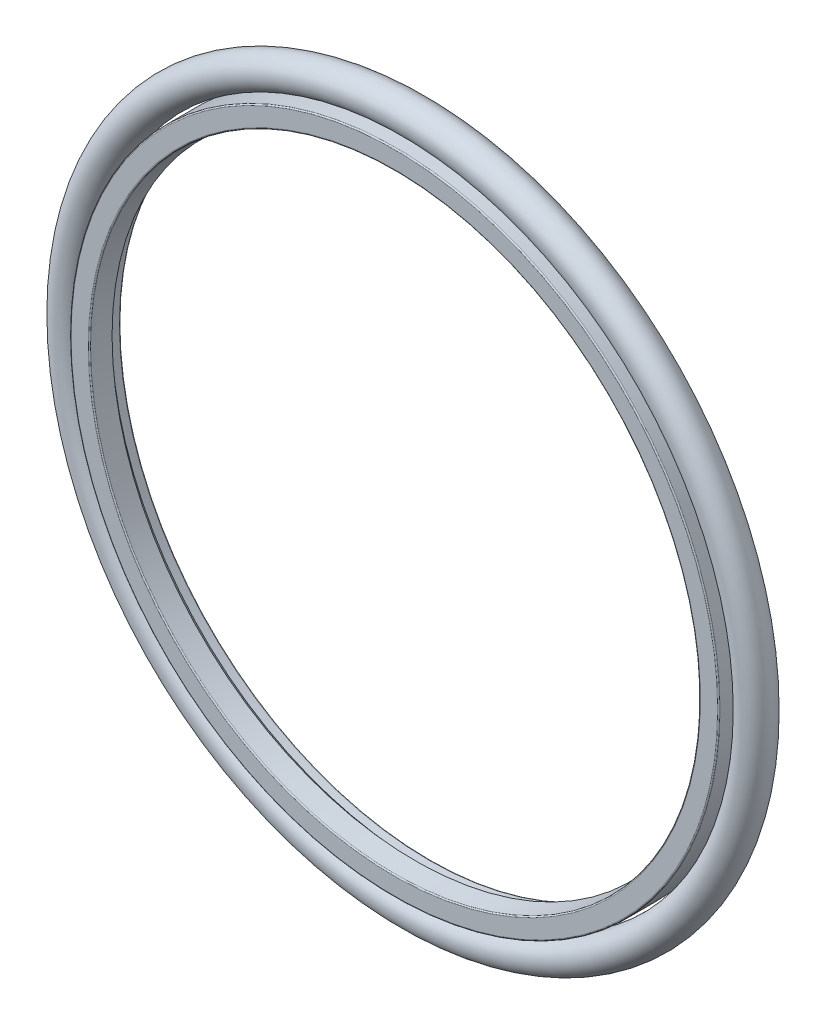
SolidWorks part; units mm, degrees
material "PTFE+NBR"
ref_plane "Front Plane" through (0, 0, 0) normal (0, 0, 1) x (1, 0, 0)
ref_plane "Top Plane" through (0, 0, 0) normal (0, 1, 0) x (1, 0, 0)
ref_plane "Right Plane" through (0, 0, 0) normal (1, 0, 0) x (0, 0, -1)
sketch "Sketch1" plane through (0, 0, 0) normal (1, 0, 0) x (0, 0, -1)
  line L0 (0, 51.05) -> (0, 53.05)
  line L1 (-0.2, 53.25) -> (-5.72, 53.25)
  line L2 (-5.92, 53.05) -> (-5.92, 50.2332)
  line L3 (-5.7375, 50.034) -> (-2.5, 49.75)
  line L5 (-1.5, 50.85) -> (-2.5, 49.75)
  line L6 (0, 0) -> (-16.4728, 0) construction
  line L7 (-0.2, 50.85) -> (-1.5, 50.85)
  arc A0 (-0.2, 53.25) -> (0, 53.05) centre (-0.2, 53.05) cw
  arc A1 (0, 51.05) -> (-0.2, 50.85) centre (-0.2, 51.05) cw
  arc A3 (-5.92, 50.2332) -> (-5.7375, 50.034) centre (-5.72, 50.2332) ccw
  arc A4 (-5.72, 53.25) -> (-5.92, 53.05) centre (-5.72, 53.05) ccw
  point P11 (0, 50.85)
  point P19 (-5.92, 50.05)
  point P22 (-5.92, 53.25)
  dimension "D2" = 0.2
  dimension "D4" = 0.2
  dimension "D10" = 3.5
  dimension "D11" = 100.1
  dimension "D5" = 0.2
  dimension "D1" = 5.92
  dimension "D3" = 106.5
  dimension "D6" = 2.4
  dimension "D7" = 1.5
  dimension "D8" = 2.5
  dimension "D9" = 3.2
  dimension "D12" = 99.5
  dimension "D13" = 101.7
revolve "Revolve1" add sketch "Sketch1" angle 360 about L6
sketch "Sketch4" plane through (0, 0, 0) normal (1, 0, 0) x (0, 0, -1)
  line L0 (0, 0) -> (-5.72, 0) construction
  line L1 (-5.72, 53.25) -> (-5.72, -53.25) construction
  line L2 (-2.86, 0) -> (-2.86, 52.8756) construction
  circle A0 centre (-2.86, 56.325) radius 2.665
  dimension "D1" = 107.32
  dimension "D2" = 5.33
revolve "Revolve2" add sketch "Sketch4" angle 360 about L0
ref_axis "Axis1" through (0, 0, 0) along (0, 0, 1)
ref_plane "Plane1" through (0, 0, 0) normal (0.7071, -0.7071, 0) x (0.7071, 0.7071, 0)
